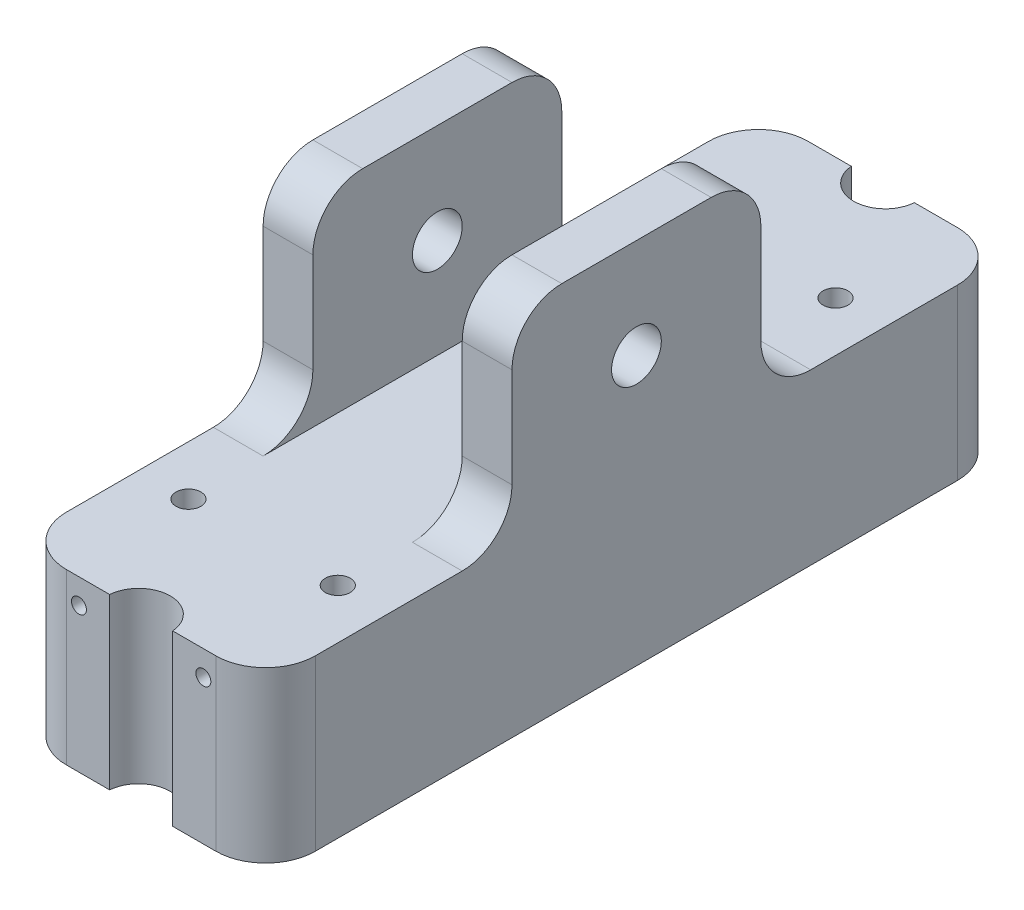
SolidWorks part; units mm, degrees
material "Nylon 101"
ref_plane "Front" through (0, 0, 0) normal (0, 0, 1) x (1, 0, 0)
ref_plane "Top" through (0, 0, 0) normal (0, 1, 0) x (1, 0, 0)
ref_plane "Right" through (0, 0, 0) normal (1, 0, 0) x (0, 0, -1)
sketch "Sketch1" plane through (0, 0, 0) normal (0, 1, 0) x (1, 0, 0)
  line L0 (-25, -75) -> (25, -75) construction
  line L1 (-15, 50) -> (15, 50) construction
  line L2 (0, -75) -> (0, 75) construction
  line L3 (-25, -75) -> (-25, 75)
  line L4 (25, -75) -> (25, 75)
  line L5 (25, 0) -> (0, 0) construction
  line L6 (25, 17) -> (97.2, 17)
  line L7 (25, 17) -> (25, -17)
  line L8 (25, -17) -> (97.2, -17)
  line L9 (97.2, 17) -> (97.2, -17)
  line L10 (-15, 50) -> (-15, -50) construction
  line L11 (-15, -50) -> (15, -50) construction
  line L12 (15, 50) -> (15, -50) construction
  line L13 (-25, -75.5) -> (25, -75.5)
  line L14 (-25, -74.5) -> (25, -74.5)
  line L15 (-25, 75.5) -> (25, 75.5)
  line L16 (-25, 74.5) -> (25, 74.5)
  circle A0 centre (0, 75) radius 6.35
  circle A1 centre (0, -75) radius 6.35
  arc A2 (-25, -75) -> (25, -75) centre (0, -75) ccw
  arc A3 (25, 75) -> (-25, 75) centre (0, 75) ccw
  circle A6 centre (-15, 50) radius 2.5
  circle A7 centre (-15, -50) radius 2.5
  circle A8 centre (15, -50) radius 2.5
  circle A9 centre (15, 50) radius 2.5
  point P8 (0, 0)
  point P24 (0, -50)
  dimension "D2" = 12.7
  dimension "D5" = 25
  dimension "D1" = 5
  dimension "D3" = 150
  dimension "D4" = 25
  dimension "D6" = 25
  dimension "D7" = 34
  dimension "D8" = 72.2
  dimension "D9" = 30
  dimension "D10" = 0.5
  dimension "D11" = 0.5
extrude "Boss-Extrude1" add sketch "Sketch1" along normal blind 10 and the other way blind 24.004 contours A1 L14 L4 L16 A0 L3 A9 A8 A7 A6 region at (0, 0, 0)
sketch "Sketch2" plane through (0, 0, 0) normal (0, 1, 0) x (1, 0, 0)
  line L0 (25, -75) -> (25, 75) construction
  line L1 (25, 25) -> (15, 25)
  line L2 (25, 25) -> (25, -25)
  line L3 (25, -25) -> (15, -25)
  line L4 (15, 25) -> (15, -25)
  line L6 (25, 0) -> (0, 0) construction
  line L7 (25, 0) -> (0, 0) construction
  line L8 (-25, -74.5) -> (-25, 74.5) construction
  line L9 (-25, 25) -> (-15, 25)
  line L10 (-25, 25) -> (-25, -25)
  line L11 (-25, -25) -> (-15, -25)
  line L12 (-15, 25) -> (-15, -25)
  line L13 (0, 0) -> (0, 4.5574) construction
  dimension "D1" = 50
  dimension "D2" = 10
extrude "Boss-Extrude2" add sketch "Sketch2" along normal blind 50
sketch "Sketch4" plane through (25, 0, 0) normal (1, 0, 0) x (0, 0, -1)
  line L0 (-25, 10) -> (25, 10) construction
  line L1 (-74.5, 10) -> (-25, 10) construction
  line L2 (-25, 50) -> (-25, 10) construction
  line L3 (0, 10) -> (0, 50) construction
  line L4 (-25, 50) -> (25, 50) construction
  circle A0 centre (0, 30) radius 5
  dimension "D1" = 10
extrude "Cut-Extrude2" cut sketch "Sketch4" against normal through all
fillet "Fillet1" radius 10 12 edges at (-20, 50, -25) (-20, 50, 25) (-20, 10, 25) (-20, 10, -25) (20, 50, -25) (20, 50, 25) (20, 10, 25) (20, 10, -25) (25, -7.002, -74.5) (-25, -7.002, -74.5) (-25, -7.002, 74.5) (25, -7.002, 74.5)
sketch "Sketch5" plane through (0, 0, 74.5) normal (0, 0, 1) x (1, 0, 0)
  line L0 (-12.5, 0) -> (-12.5, 10) construction
  line L1 (12.5, 10) -> (12.5, 0) construction
  line L2 (-15, 10) -> (-6.3303, 10) construction
  line L3 (6.3303, 10) -> (15, 10) construction
  line L4 (0, 0) -> (0, 2.4841) construction
  circle A0 centre (-12.5, 5) radius 1.5
  circle A1 centre (12.5, 5) radius 1.5
  dimension "D1" = 3
  dimension "D2" = 12.5
extrude "Cut-Extrude3" cut sketch "Sketch5" against normal blind 5
extrude "Cut-Extrude4" cut sketch "Sketch5<2>" along normal blind 5 from surface starting at face at (10.6651, -7.002, -74.5)
sketch "Sketch5<2>" plane through (0, 0, 74.5) normal (0, 0, 1) x (1, 0, 0) same geometry as "Sketch5"
